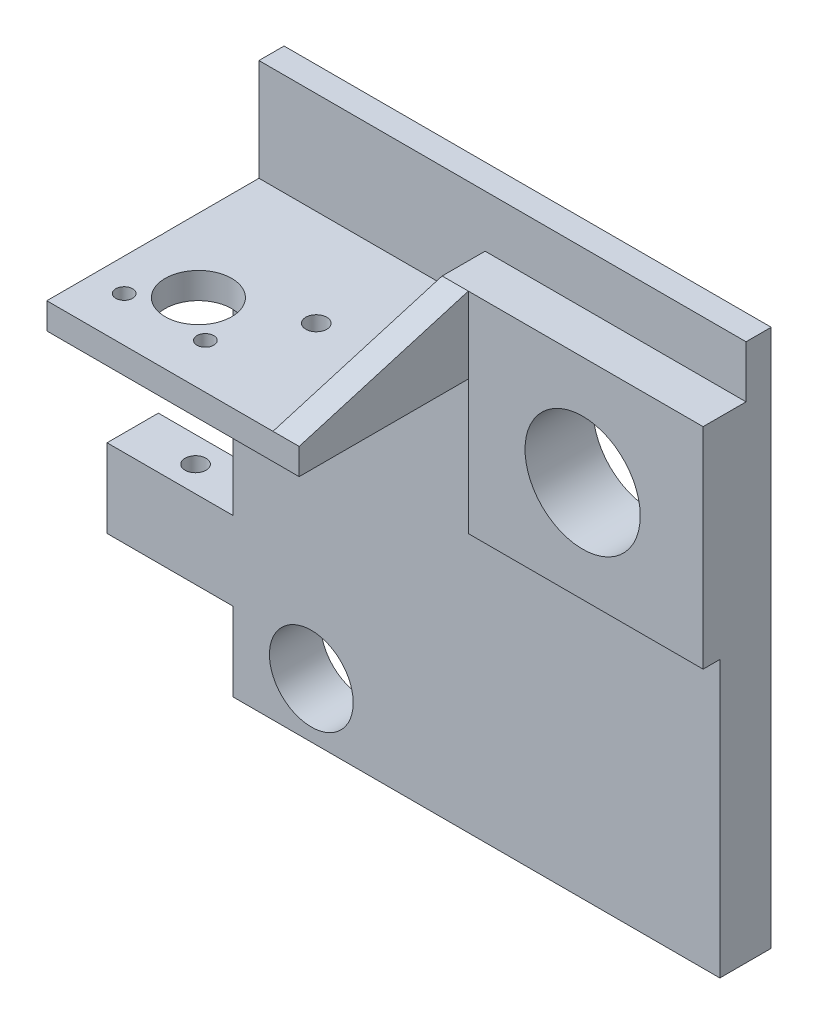
SolidWorks part; units mm, degrees
material "ABS"
ref_plane "Front Plane" through (0, 0, 0) normal (0, 0, 1) x (1, 0, 0)
ref_plane "Top Plane" through (0, 0, 0) normal (0, 1, 0) x (1, 0, 0)
ref_plane "Right Plane" through (0, 0, 0) normal (1, 0, 0) x (0, 0, -1)
sketch "Sketch1" plane through (0, 0, 0) normal (0, 0, 1) x (1, 0, 0)
  line L0 (-24, 15) -> (0, 15)
  line L1 (0, 15) -> (0, 0)
  line L2 (0, 0) -> (93, 0)
  line L3 (93, 0) -> (93, 102.7)
  line L4 (93, 102.7) -> (0, 102.7)
  line L5 (0, 102.7) -> (0, 30)
  line L6 (0, 30) -> (-24, 30)
  line L7 (-24, 30) -> (-24, 15)
  circle A0 centre (15, 10.5) radius 8
  circle A1 centre (70, 72) radius 11
  circle A2 centre (15, 10.5) radius 11
  dimension "D1" = 15
  dimension "D10" = 16
  dimension "D11" = 22
  dimension "D12" = 22
  dimension "D2" = 24
  dimension "D3" = 72.7
  dimension "D4" = 15
  dimension "D5" = 15
  dimension "D6" = 10.5
  dimension "D7" = 82.5061
  dimension "D8" = 72
  dimension "D9" = 93
extrude "Boss-Extrude1" add sketch "Sketch1" along normal blind 4.8 contours A2 L2 L3 L4 L5 L6 L7 L0 L1 A1 | L2 A2 A0 region at (44.5238, 51.0418, 0) region at (8.6656, 19.1141, 0)
sketch "Sketch2" plane through (0, 0, 4.8) normal (0, 0, 1) x (1, 0, 0)
  line L0 (93, 0) -> (93, 102.7) construction
  line L1 (48.1786, 92.7632) -> (93, 92.7632)
  line L2 (48.1786, 92.7632) -> (48.1786, 52.666)
  line L3 (48.1786, 52.666) -> (93, 52.666)
  line L4 (93, 92.7632) -> (93, 52.666)
  line L5 (48.1786, 92.7632) -> (93, 52.666) construction
  line L6 (48.1786, 52.666) -> (93, 92.7632) construction
  circle A0 centre (70, 72) radius 11
  circle A1 centre (70, 72) radius 4.15
  point P8 (70.5893, 72.7146)
  line M4 (93, 0) -> (93, 102.7)
  circle M10 centre (70, 72) radius 11
  dimension "D1" = 22
  dimension "D2" = 8.3
extrude "Boss-Extrude2" add sketch "Sketch2" along normal blind 8.2 contours L2 L3 L1 M4 M10 region at (70.5893, 92.1618, 4.8)
sketch "Sketch3" plane through (0, 0, 4.8) normal (0, 0, 1) x (1, 0, 0)
  line L1 (-24, 15) -> (0, 15)
  line L2 (-24, 15) -> (-24, 30)
  line L3 (-24, 30) -> (0, 30)
  line L4 (0, 15) -> (0, 30)
  line L5 (-24, 15) -> (0, 30) construction
  line L6 (-24, 30) -> (0, 15) construction
  line L7 (0, 0) -> (93, 0)
  line L8 (0, 0) -> (0, 52.666)
  line L9 (0, 52.666) -> (93, 52.666)
  line L10 (93, 0) -> (93, 52.666)
  line L11 (0, 0) -> (93, 52.666) construction
  line L12 (0, 52.666) -> (93, 0) construction
  circle A0 centre (15, 10.5) radius 8
  point P4 (-12, 22.5)
  point P11 (46.5, 26.333)
  circle M1 centre (15, 10.5) radius 8
  line M6 (0, 102.7) -> (0, 30)
  line M7 (0, 30) -> (-24, 30)
  line M8 (-24, 30) -> (-24, 15)
  line M9 (-24, 15) -> (0, 15)
  line M10 (0, 15) -> (0, 0)
  line M11 (0, 0) -> (93, 0)
  line M12 (93, 0) -> (93, 52.666)
  line M13 (93, 52.666) -> (48.1786, 52.666)
extrude "Boss-Extrude3" add sketch "Sketch3" along normal blind 5 contours L4 M9 M7 M8 | L9 L4 M6 M10 M11 M12 M13 M1 region at (-12, 22.5, 4.8) region at (47.8484, 27.0108, 4.8)
sketch "Sketch4" plane through (0, 83.2317, 0) normal (0, -1, 0) x (1, 0, 0)
  line L0 (0, 9.8) -> (0, 4.8) construction
  line L1 (0, 4.8) -> (48.1786, 4.8)
  line L2 (0, 4.8) -> (0, 45.3)
  line L3 (0, 45.3) -> (48.1786, 45.3)
  line L4 (48.1786, 4.8) -> (48.1786, 45.3)
  line L5 (0, 4.8) -> (48.1786, 45.3) construction
  line L6 (0, 45.3) -> (48.1786, 4.8) construction
  line L7 (0, 4.8) -> (48.1786, 4.8) construction
  line L8 (48.1786, 13) -> (48.1786, 9.8) construction
  line L9 (0, 0) -> (93, 0) construction
  line L10 (0, 45.3) -> (-5, 45.3)
  line L11 (0, 45.3) -> (0, 0)
  line L12 (0, 0) -> (-5, 0)
  line L13 (-5, 45.3) -> (-5, 0)
  line L14 (0, 45.3) -> (-5, 0) construction
  line L15 (0, 0) -> (-5, 45.3) construction
  circle A0 centre (13.9465, 30.3) radius 6.35
  circle A1 centre (13.9465, 23.3) radius 18.5
  circle A3 centre (29.4465, 23.3) radius 2
  circle A4 centre (21.6965, 9.8766) radius 2
  circle A5 centre (6.1965, 9.8766) radius 2
  point P10 (24.0893, 25.05)
  point P30 (-2.5, 22.65)
  arc M5 (5.039, 30.9329) -> (22.854, 30.9329) centre (13.9465, 30.3) ccw
  arc M7 (23.1854, 31.0672) -> (4.7077, 31.0672) centre (13.9465, 23.3) cw
  circle M9 centre (21.6965, 9.8766) radius 1.6
  circle M10 centre (6.1965, 9.8766) radius 1.6
  circle M11 centre (-1.5535, 23.3) radius 1.6
  circle M12 centre (6.1965, 36.7234) radius 1.6
  circle M13 centre (21.6965, 36.7234) radius 1.6
  circle M15 centre (27.3699, 31.05) radius 2.1
  circle M16 centre (0.5231, 31.05) radius 2.1
  circle M17 centre (13.9465, 7.8) radius 2.1
  circle M19 centre (13.9465, 23.3) radius 18.5
  dimension "D1" = 12.7
  dimension "D2" = 15
  dimension "D3" = 4
  dimension "D4" = 4
  dimension "D5" = 4
  dimension "D6" = 5
  dimension "D7" = 0
extrude "Boss-Extrude4" add sketch "Sketch4" along normal blind 5 contours L1 L4 L3 M19 | A0 L3 L2 A5 A4 A3 M12 M19 M16 M11 M13 M17 M15 M5 M7 | M5 M7 | M17 | A4 M9 | M9 | M10 | A5 M10 | M15 | L2 M16 | L2 L1 M19 region at (3.3557, 83.2317, 6.6306) region at (34.3643, 83.2317, 27.4815) region at (15.1399, 83.2317, 22.3686) region at (1.1393, 83.2317, 31.05) region at (19.7531, 83.2317, 9.8766) region at (4.2531, 83.2317, 9.8766) region at (21.6965, 83.2317, 9.8766) region at (6.1965, 83.2317, 9.8766) region at (27.3699, 83.2317, 31.05) region at (13.9465, 83.2317, 7.8)
sketch "Sketch5" plane through (48.1786, 0, 0) normal (1, 0, 0) x (0, 0, -1)
  line L0 (-45.3, 83.2317) -> (-13, 92.7632)
  line L1 (-13, 92.7632) -> (-4.8, 92.7632)
  line L2 (-4.8, 92.7632) -> (-4.8, 78.2317)
  line L3 (-4.8, 78.2317) -> (-45.3, 78.2317)
  line L4 (-45.3, 78.2317) -> (-45.3, 83.2317)
extrude "Boss-Extrude5" add sketch "Sketch5" against normal blind 5
sketch "Sketch6" plane through (0, 0, 4.8) normal (0, 0, 1) x (1, 0, 0)
  line L0 (0, 78.2317) -> (0, 52.666) construction
  line L1 (0, 78.2317) -> (48.1786, 78.2317)
  line L2 (0, 78.2317) -> (0, 52.666)
  line L3 (0, 52.666) -> (48.1786, 52.666)
  line L4 (48.1786, 78.2317) -> (48.1786, 52.666)
  line L5 (0, 78.2317) -> (48.1786, 52.666) construction
  line L6 (0, 52.666) -> (48.1786, 78.2317) construction
  line L7 (0, 78.2317) -> (48.1786, 78.2317) construction
  point P4 (24.0893, 65.4489)
extrude "Boss-Extrude6" add sketch "Sketch6" along normal up to surface (5 mm away) up to face at (20.6865, 27.5553, 9.8)
ref_plane "Plane1" through (3.9877, 7.5909, 34.4544) normal (0.9262, 0.2454, -0.2862) x (0.0581, -0.8429, -0.5349)
sketch "Sketch8" plane through (0, 30, 0) normal (0, 1, 0) x (1, 0, 0)
  line L0 (0, 0) -> (-24, -9.8)
  line L1 (-24, -9.8) -> (-24, 0)
  line L2 (-24, 0) -> (0, -9.8)
  circle A0 centre (-12, -4.9) radius 2
  dimension "D1" = 4
extrude "Cut-Extrude1" cut sketch "Sketch8" against normal through all contours A0
